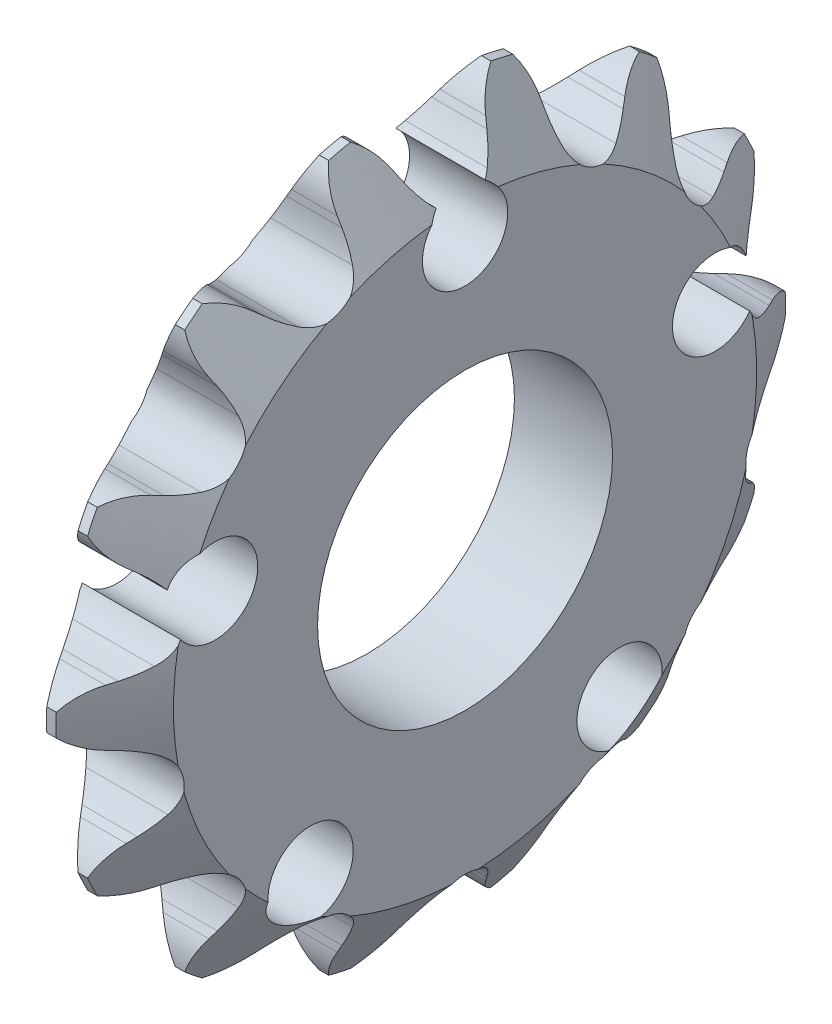
SolidWorks part; units mm, degrees
material "Alloy Steel"
ref_plane "Front Plane" through (0, 0, 0) normal (0, 0, 1) x (1, 0, 0)
ref_plane "Top Plane" through (0, 0, 0) normal (0, 1, 0) x (1, 0, 0)
ref_plane "Right Plane" through (0, 0, 0) normal (1, 0, 0) x (0, 0, -1)
ref_axis "X AXIS" through (-88.99, 0, 0) along (1, 0, 0)
ref_axis "Y AXIS" through (0, -55, 0) along (0, 1, 0)
ref_axis "Z AXIS" through (0, 0, 55) along (0, 0, -1)
other "Freeze***"
sketch "Sketch1" plane through (0, 0, 0) normal (1, 0, 0) x (0, 0, -1)
  line L0 (0, 14.2683) -> (-6.1908, 12.8553) construction
  line L1 (-1.8786, 14.0876) -> (-2.0306, 14.4094)
  line L2 (-1.8786, 14.0876) -> (2.0446, 15.9409) construction
  line L3 (2.0446, 15.9409) -> (0, 14.2683) construction
  line L4 (0, 14.2683) -> (-1.964, 14.2683) construction
  line L5 (-3.6127, 15.8282) -> (-3.0954, 13.5618) construction
  line L6 (0, 14.2683) -> (0, 12.571) construction
  circle A0 centre (0, 0) radius 14.2683 construction
  arc A1 (-1.3137, 13.1936) -> (0, 12.571) centre (0, 14.2683) ccw
  arc A2 (-1.3137, 13.1936) -> (-1.8786, 14.0876) centre (2.0446, 15.9409) cw
  arc A3 (-2.0306, 14.4094) -> (-3.6127, 15.8282) centre (-4.5069, 13.2397) ccw
sketch "Sketch2" plane through (0, 0, 0) normal (0, 0, 1) x (1, 0, 0)
  line L0 (0, 0) -> (0, 15.8558) construction
  line L1 (-0.2064, 15.8558) -> (0.2064, 15.8558)
  line L2 (0.2064, 15.8558) -> (2.1336, 12.6808)
  line L3 (2.1336, 12.6808) -> (2.1336, 0)
  line L4 (-2.1336, 0) -> (2.1336, 0)
  line L5 (-2.1336, 12.6808) -> (-2.1336, 0)
  line L6 (-0.2064, 15.8558) -> (-2.1336, 12.6808)
  dimension "D1" = 15.8558
  dimension "D2" = 4.2672
revolve "Revolve1" add sketch "Sketch2" angle 360 about L4
sketch "Sketch3" plane through (0, 0, 0) normal (1, 0, 0) x (0, 0, -1)
  line L0 (-1.8786, 14.0876) -> (-2.0306, 14.4094) construction
  line L1 (-1.8786, 14.0876) -> (-2.0306, 14.4094)
  line L2 (0, 12.571) -> (0, 0) construction
  line L3 (1.8786, 14.0876) -> (2.0306, 14.4094)
  arc A0 (-2.0306, 14.4094) -> (-3.6127, 15.8282) centre (-4.5069, 13.2397) ccw construction
  arc A1 (-1.8786, 14.0876) -> (-1.3137, 13.1936) centre (2.0446, 15.9409) ccw construction
  arc A2 (-1.3137, 13.1936) -> (0, 12.571) centre (0, 14.2683) ccw construction
  arc A3 (-2.0306, 14.4094) -> (-3.6127, 15.8282) centre (-4.5069, 13.2397) ccw
  arc A4 (-1.8786, 14.0876) -> (-1.3137, 13.1936) centre (2.0446, 15.9409) ccw
  arc A5 (-1.3137, 13.1936) -> (1.3137, 13.1936) centre (0, 14.2683) ccw
  arc A6 (1.8786, 14.0876) -> (1.3137, 13.1936) centre (-2.0446, 15.9409) cw
  arc A7 (2.0306, 14.4094) -> (3.6127, 15.8282) centre (4.5069, 13.2397) cw
  arc A8 (-3.6127, 15.8282) -> (3.6127, 15.8282) centre (0, 0) cw
extrude "Cut-Extrude1" cut sketch "Sketch3" against normal through all both and the other way through all contours A8 A3 L1 A4 A5 A6 L3 A7 region at (0, 14.7383, 0)
pattern_circular "CirPattern1" count 14 over 360 about axis through (-88.99, 0, 0) along (1, 0, 0) of "Cut-Extrude1"
sketch "Sketch4" plane through (2.1336, 0, 0) normal (1, 0, 0) x (0, 0, -1)
  line L0 (0, 0) -> (0, 11.43) construction
  circle A0 centre (0, 0) radius 6.4135
  circle A1 centre (0, 11.43) radius 1.8542
  circle A2 centre (10.8706, 3.5321) radius 1.8542
  circle A3 centre (6.7184, -9.2471) radius 1.8542
  circle A4 centre (-6.7184, -9.2471) radius 1.8542
  circle A5 centre (-10.8706, 3.5321) radius 1.8542
  point P15 (0, 0)
  dimension "D1" = 12.827
  dimension "D2" = 5
  dimension "D3" = 3.7084
  dimension "D4" = 11.43
extrude "Cut-Extrude2" cut sketch "Sketch4" against normal through all
equation "\"p\" = 2 / 8"
equation "\"n\"= 14"
equation "\"Dr\"= 0.13"
equation "\"Ds\"= 1.005 * \"Dr\" + 0.003"
equation "\"PD\"= \"p\" * cosec ( 180 / \"n\" )"
equation "\"A\"= 35 + 60 / \"n\""
equation "\"B\"= 18 - 56 / \"n\""
equation "\"ac\"= 0.8 * \"Dr\""
equation "\"ab\"= 1.4 * \"Dr\""
equation "\"D1@Sketch1\"=\"PD\""
equation "\"D2@Sketch1\"=\"p\""
equation "\"D3@Sketch1\"=\"Ds\""
equation "\"D4@Sketch1\"=\"A\""
equation "\"D5@Sketch1\"=\"B\""
equation "\"D6@Sketch1\"=\"ac\""
equation "\"D7@Sketch1\"=\"ab\""
equation "\"D1@Sketch2\"=(\"PD\"+\"p\"/2)/2"
equation "\"D4@Sketch2\"=\"p\"/2"
equation "\"D1@CirPattern1\"=\"n\""
